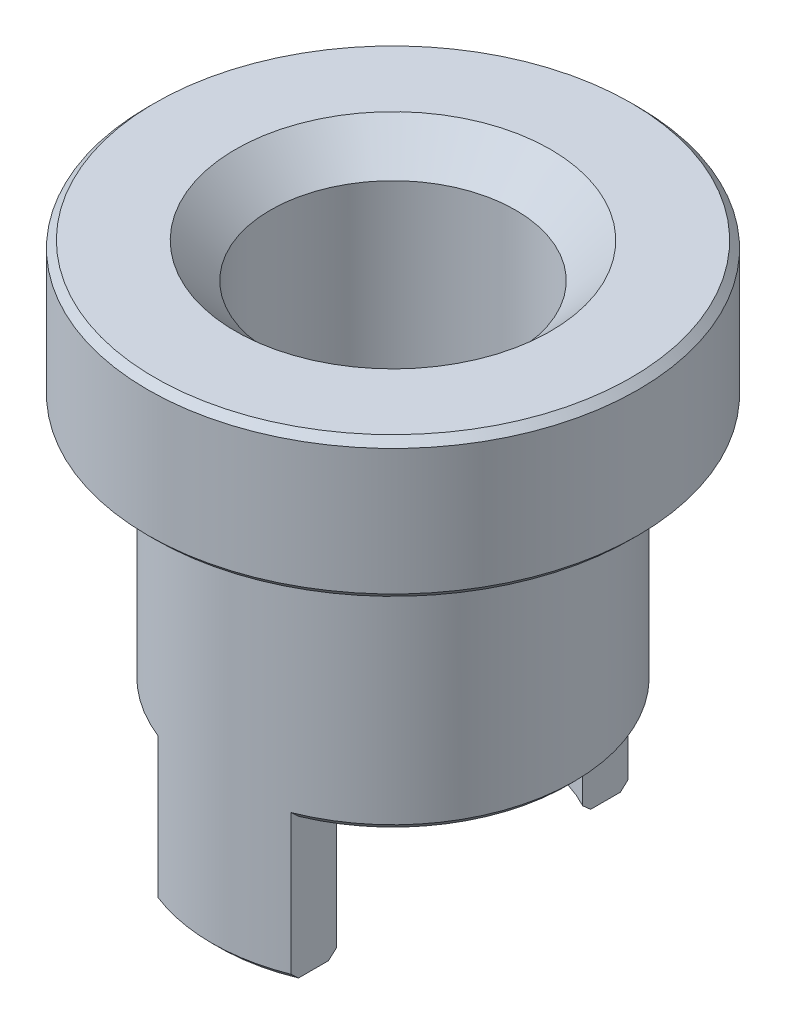
SolidWorks part; units mm, degrees
material "Латунь"
ref_plane "Спереди" through (0, 0, 0) normal (0, 0, 1) x (1, 0, 0)
ref_plane "Сверху" through (0, 0, 0) normal (0, 1, 0) x (1, 0, 0)
ref_plane "Справа" through (0, 0, 0) normal (1, 0, 0) x (0, 0, -1)
sketch "Эскиз1" plane through (0, 0, 0) normal (1, 0, 0) x (0, 0, -1)
  line L0 (0, 26.7622) -> (0, -27.4451) construction
  line L1 (0, 0) -> (5.175, 0)
  line L2 (5.175, 0) -> (5.175, 11)
  line L3 (5.175, 11) -> (7, 11)
  line L4 (7, 11) -> (7, 15)
  line L5 (7, 15) -> (0, 15)
  line L6 (0, 15) -> (3.5, 15)
  line L7 (3.5, 15) -> (3.5, 0)
  dimension "D1" = 7
  dimension "D2" = 10.35
  dimension "D3" = 14
  dimension "D4" = 4
  dimension "D5" = 15
revolve "Повернуть1" add sketch "Эскиз1" angle 360 about L0
sketch "Эскиз2" plane through (0, 0, 0) normal (0, 0, 1) x (1, 0, 0)
  line L0 (0, 15.478) -> (0, -0.3221) construction
  line L2 (1.9, 0) -> (1.9, 4)
  line L3 (-5.175, 0) -> (5.175, 0) construction
  line L4 (1.9, 4) -> (5.175, 4)
  line L5 (5.175, 0) -> (5.175, 11) construction
  line L6 (5.175, 4) -> (5.175, 0)
  line L7 (5.175, 0) -> (1.9, 0)
  line L8 (-5.175, 0) -> (-5.175, 4)
  line L9 (-5.175, 4) -> (-1.9, 4)
  line L10 (-1.9, 4) -> (-1.9, 0)
  line L11 (-1.9, 0) -> (-5.175, 0)
  point P6 (0, 0)
  dimension "D1" = 3.8
  dimension "D2" = 4
extrude "Вырез-Вытянуть1" cut sketch "Эскиз2" against normal through all both and the other way through all
sketch "Эскиз3" plane through (0, 4, 0) normal (0, -1, 0) x (1, 0, 0)
  circle A0 centre (0, 0) radius 4
  dimension "D1" = 8
extrude "Вырез-Вытянуть2" cut sketch "Эскиз3" along normal blind 4
chamfer "Фаска1" distance 1 angle 45 2 edges at (0, 4, 3.5) (0, 15, 3.5)
chamfer "Фаска2" distance 0.2 angle 45 8 edges at (0, 11, 7) (0, 15, 7) (0, 11, 5.175) (5.175, 4, 0) (0, 0, -5.175) (0, 0, 5.175) (0, 0, 4) (0, 0, -4)
